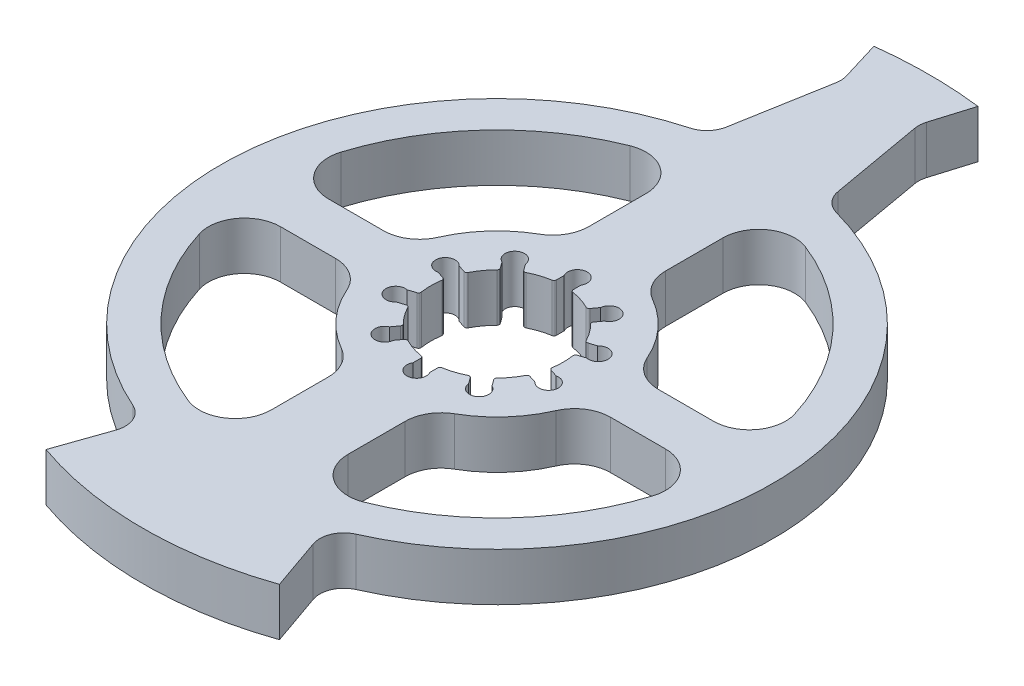
SolidWorks part; units mm, degrees
material "AISI Type A2 Tool Steel"
ref_plane "Front Plane" through (0, 0, 0) normal (0, 0, 1) x (1, 0, 0)
ref_plane "Top Plane" through (0, 0, 0) normal (0, 1, 0) x (1, 0, 0)
ref_plane "Right Plane" through (0, 0, 0) normal (1, 0, 0) x (0, 0, -1)
other "Center of Mass"
other "Bounding Box"
ref_plane "Default Plane" through (0, 2.286, 19.05) normal (0, -1, 0) x (-1, 0, 0)
sketch "Sketch1" plane through (0, 0, 0) normal (0, 1, 0) x (1, 0, 0)
  circle A0 centre (0, 0) radius 114.3 construction
  circle A1 centre (0, 0) radius 73.025
  circle A2 centre (0, 0) radius 17.4625
  dimension "D1" = 228.6
  dimension "D2" = 146.05
  dimension "D3" = 34.925
extrude "Boss-Extrude1" add sketch "Sketch1" along normal mid plane 12.7
sketch "Sketch2" plane through (0, 6.35, 0) normal (0, 1, 0) x (1, 0, 0)
  line L0 (-10.16, 101.6) -> (-15.4916, 71.3629)
  line L1 (15.4916, 71.3629) -> (10.16, 101.6)
  line L2 (10.16, 101.6) -> (13.77, 113.4675)
  line L3 (-10.16, 101.6) -> (-13.77, 113.4675)
  line L4 (0, 0) -> (0, 114.3) construction
  line L5 (-10.16, 101.6) -> (0, 101.6) construction
  line L6 (0, 101.6) -> (10.16, 101.6) construction
  line L7 (-13.77, 113.4675) -> (0, 0) construction
  circle A0 centre (0, 0) radius 114.3 construction
  circle A1 centre (0, 0) radius 114.3 construction
  arc A2 (-13.77, 113.4675) -> (13.77, 113.4675) centre (0, 0) cw
  circle A5 centre (0, 0) radius 73.025
  arc A6 (15.4916, 71.3629) -> (-15.4916, 71.3629) centre (0, 0) ccw
  arc A7 (-15.4916, 71.3629) -> (15.4916, 71.3629) centre (0, 0) ccw construction
  dimension "D3" = 10
  dimension "D4" = 12.7
  dimension "D5" = 10
  dimension "D6" = 10.16
  dimension "D2" = 0
extrude "Boss-Extrude2" add sketch "Sketch2" against normal through all
sketch "Sketch3" plane through (0, 6.35, 0) normal (0, 1, 0) x (1, 0, 0)
  line L0 (-30.8797, -88.4257) -> (-24.0757, -68.9421)
  line L1 (24.0757, -68.9421) -> (30.8797, -88.4257)
  line L2 (0, -73.025) -> (0, -93.6625) construction
  line L3 (0, -93.6625) -> (0, -114.3) construction
  line L4 (-24.0757, -68.9421) -> (0, 0) construction
  line L5 (0, 0) -> (24.0757, -68.9421) construction
  arc A0 (-30.8797, -88.4257) -> (30.8797, -88.4257) centre (0, 0) ccw
  circle A1 centre (0, 0) radius 73.025 construction
  circle A2 centre (0, 0) radius 114.3 construction
  arc A3 (-24.0757, -68.9421) -> (24.0757, -68.9421) centre (0, 0) ccw
  point P13 (0, -93.6625)
  dimension "D1" = 38.5
extrude "Boss-Extrude3" add sketch "Sketch3" against normal through all
sketch "Sketch4" plane through (0, 6.35, 0) normal (0, 1, 0) x (1, 0, 0)
  line L0 (0, 0) -> (-73.025, 0) construction
  line L1 (-62.5435, -6.35) -> (-29.4865, -6.35)
  line L4 (-10.16, -62.0386) -> (-10.16, -28.3998)
  line L8 (0, -93.6625) -> (0, 0) construction
  arc A0 (-10.16, -28.3998) -> (-29.4865, -6.35) centre (0, 0) cw
  arc A1 (-10.16, -62.0386) -> (-62.5435, -6.35) centre (0, 0) cw
  circle A2 centre (0, 0) radius 73.025 construction
  arc A5 (-30.8797, -88.4257) -> (30.8797, -88.4257) centre (0, 0) ccw construction
  arc A6 (-15.4916, 71.3629) -> (-24.0757, -68.9421) centre (0, 0) ccw construction
  circle A7 centre (0, 0) radius 17.4625 construction
  dimension "D1" = 10.16
  dimension "D2" = 12.7
  dimension "D3" = 10.16
  dimension "D4" = 6.35
extrude "Cut-Extrude1" cut sketch "Sketch4" against normal through all
mirror "Mirror1" about plane through (0, 0, 0) normal (1, 0, 0) of "Cut-Extrude1"
mirror "Mirror2" about plane through (0, 0, 0) normal (0, 0, 1) of "Mirror1"
sketch "Sketch5" plane through (0, 6.35, 0) normal (0, 1, 0) x (1, 0, 0)
  line L0 (0, 17.4625) -> (0, 21.2725) construction
  line L2 (-2.2225, 17.3205) -> (2.2225, 17.3205)
  line L3 (-2.2225, 17.3205) -> (-2.2225, 19.9912)
  line L5 (2.2225, 17.3205) -> (2.2225, 19.9912)
  arc A0 (2.2225, 19.9912) -> (-2.2225, 19.9912) centre (0, 21.2725) ccw
  circle A1 centre (0, 0) radius 17.4625 construction
  circle A2 centre (0, 21.2725) radius 4.5847 construction
  dimension "D2" = 5.1308
  dimension "D4" = 9.1694
  dimension "D1" = 3.81
  dimension "D3" = 4.445
extrude "Cut-Extrude2" cut sketch "Sketch5" against normal through all
pattern_circular "CirPattern1" count 10 over 360 about axis through (0, 6.35, 0) along (0, -1, 0) of "Cut-Extrude2"
sketch "Sketch6" plane through (0, 6.35, 0) normal (0, 1, 0) x (1, 0, 0)
  circle A0 centre (0, 0) radius 17.526
  arc A1 (-11.9788, 12.7062) -> (-15.786, 7.466) centre (0, 0) ccw construction
  dimension "D1" = 0.0635
extrude "Cut-Extrude3" cut sketch "Sketch6" against normal through all
fillet "Fillet1" radius 6.35 6 edges at (-24.0757, 0, 68.9421) (24.0757, 0, 68.9421) (15.4916, 0, -71.3629) (10.16, 0, -101.6) (-15.4916, 0, -71.3629) (-10.16, 0, -101.6)
fillet "Fillet4" radius 9.525 8 edges at (-10.16, 0, -62.0386) (-62.5435, 0, -6.35) (-62.5435, 0, 6.35) (-10.16, 0, 62.0386) (10.16, 0, 62.0386) (62.5435, 0, 6.35) (62.5435, 0, -6.35) (10.16, 0, -62.0386)
fillet "Fillet5" radius 9.525 8 edges at (-29.4865, 0, -6.35) (-10.16, 0, -28.3998) (10.16, 0, -28.3998) (29.4865, 0, -6.35) (10.16, 0, 28.3998) (29.4865, 0, 6.35) (-29.4865, 0, 6.35) (-10.16, 0, 28.3998)
fillet "Fillet6" radius 0.635 20 edges at (-12.0164, 0, -12.758) (-15.8469, 0, -7.4858) (-17.2204, 0, -3.2584) (-17.2204, 0, 3.2584) (-15.8469, 0, 7.4858) (-12.0164, 0, 12.758) (-8.4203, 0, 15.3707) (-2.2225, 0, 17.3845) (2.2225, 0, 17.3845) (8.4203, 0, 15.3707) (12.0164, 0, 12.758) (15.8469, 0, 7.4858) (17.2204, 0, 3.2584) (17.2204, 0, -3.2584) (15.8469, 0, -7.4858) (12.0164, 0, -12.758) (8.4203, 0, -15.3707) (2.2225, 0, -17.3845) (-2.2225, 0, -17.3845) (-8.4203, 0, -15.3707)
equation "\"Unit Measure\"= \"BoundingVolume\" / \"Thickness\"'in^2"
